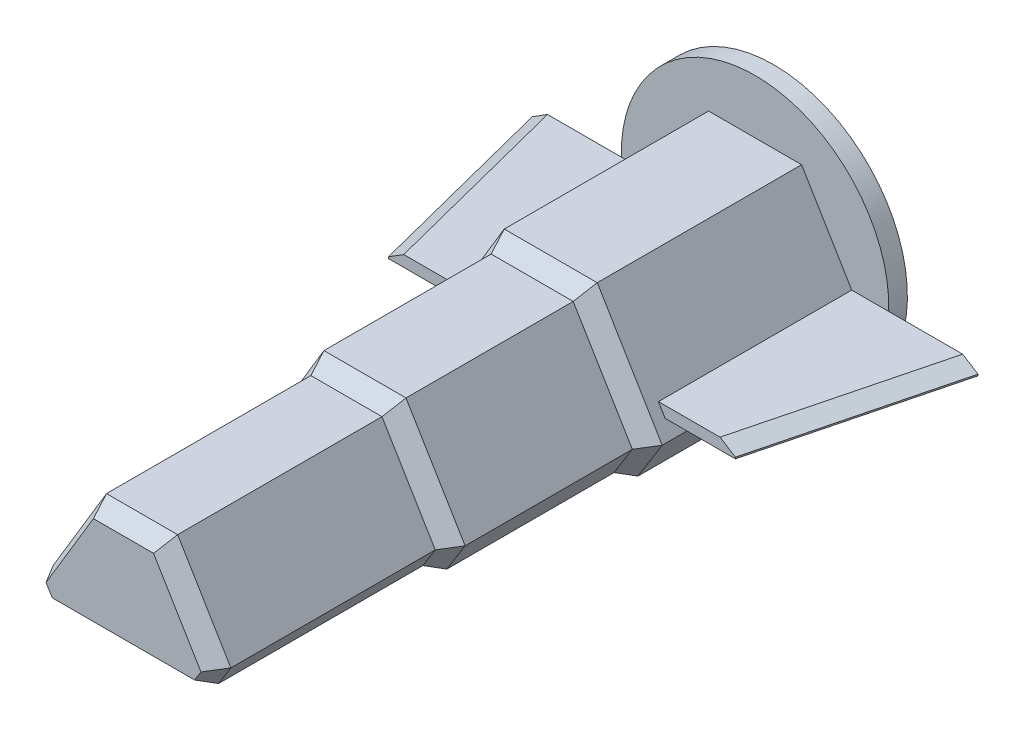
SolidWorks part; units mm, degrees
ref_plane "Front Plane" through (0, 0, 0) normal (0, 0, 1) x (1, 0, 0)
ref_plane "Top Plane" through (0, 0, 0) normal (0, 1, 0) x (1, 0, 0)
ref_plane "Right Plane" through (0, 0, 0) normal (1, 0, 0) x (0, 0, -1)
sketch "Sketch1" plane through (0, 0, 0) normal (0, 0, 1) x (1, 0, 0)
  line L0 (-26.9526, -9.3174) -> (-11.0422, 17.2)
  line L1 (23.4857, -19.8) -> (-23.4857, -19.8)
  line L2 (12.5143, 19.8) -> (-12.5143, 19.8)
  line L3 (12.5143, 19.8) -> (30, -9.3429)
  line L4 (23.4857, -19.8) -> (30, -9.3429)
  line L5 (11.0422, 17.2) -> (-11.0422, 17.2)
  line L6 (11.0422, 17.2) -> (26.9526, -9.3174)
  line L7 (-30, -9.3429) -> (-12.5143, 19.8)
  line L8 (-30, -9.3429) -> (-23.4857, -19.8)
  line L9 (22.0422, -17.2) -> (26.9526, -9.3174)
  line L10 (22.0422, -17.2) -> (-22.0422, -17.2)
  line L11 (-26.9526, -9.3174) -> (-22.0422, -17.2)
  point P0 (0, 0)
  point P4 (0, 19.8)
  point P13 (0, -19.8)
  dimension "D1" = 60
  dimension "D3" = 39.6
  dimension "D4" = 6.5143
  dimension "D5" = 10.4571
  dimension "D6" = 17.4857
  dimension "D2" = 2.6
extrude "Boss-Extrude1" add sketch "Sketch1" against normal blind 60
sketch "Sketch2" plane through (0, 0, 0) normal (0, 0, 1) x (1, 0, 0)
  line L6 (23.9053, -9.292) -> (9.5701, 14.6)
  line L7 (9.5701, 14.6) -> (-9.5701, 14.6)
  line L8 (-9.5701, 14.6) -> (-23.9053, -9.292)
  line L9 (-23.9053, -9.292) -> (-20.5986, -14.6)
  line L10 (-20.5986, -14.6) -> (20.5986, -14.6)
  line L11 (20.5986, -14.6) -> (23.9053, -9.292)
  line L12 (26.9526, -9.3174) -> (11.0422, 17.2)
  line L13 (11.0422, 17.2) -> (-11.0422, 17.2)
  line L14 (-11.0422, 17.2) -> (-26.9526, -9.3174)
  line L15 (-26.9526, -9.3174) -> (-22.0422, -17.2)
  line L16 (-22.0422, -17.2) -> (22.0422, -17.2)
  line L17 (22.0422, -17.2) -> (26.9526, -9.3174)
  line L18 (26.9526, -9.3174) -> (11.0422, 17.2)
  line L19 (11.0422, 17.2) -> (-11.0422, 17.2)
  line L20 (-11.0422, 17.2) -> (-26.9526, -9.3174)
  line L21 (-26.9526, -9.3174) -> (-22.0422, -17.2)
  line L22 (-22.0422, -17.2) -> (22.0422, -17.2)
  line L23 (22.0422, -17.2) -> (26.9526, -9.3174)
  dimension "D1" = 2.6
  dimension "D2" = 2.6
extrude "Boss-Extrude2" add sketch "Sketch2" along normal blind 50 and the other way blind 3 separate body
chamfer "Chamfer1" distance 5 distance2 2.6 6 edges at (0, -19.8, 0) (-26.7429, -14.5714, 0) (-21.2571, 5.2286, 0) (0, 19.8, 0) (26.7429, -14.5714, 0) (21.2571, 5.2286, 0) first distance on face at (0, -19.8, -30) first distance on face at (-26.7429, -14.5714, -30) first distance on face at (-21.2571, 5.2286, -30) first distance on face at (0, 19.8, -30) first distance on face at (26.7429, -14.5714, -30) first distance on face at (21.2571, 5.2286, -30)
sketch "Sketch8" plane through (0, 0, 50) normal (0, 0, 1) x (1, 0, 0)
  line L12 (19.1551, -12) -> (20.8579, -9.2665)
  line L13 (20.8579, -9.2665) -> (8.098, 12)
  line L14 (8.098, 12) -> (-8.098, 12)
  line L15 (-8.098, 12) -> (-20.8579, -9.2665)
  line L16 (-20.8579, -9.2665) -> (-19.1551, -12)
  line L17 (-19.1551, -12) -> (19.1551, -12)
  line L18 (19.1551, -12) -> (20.8579, -9.2665)
  line L19 (20.8579, -9.2665) -> (8.098, 12)
  line L20 (8.098, 12) -> (-8.098, 12)
  line L21 (-8.098, 12) -> (-20.8579, -9.2665)
  line L22 (-20.8579, -9.2665) -> (-19.1551, -12)
  line L23 (-19.1551, -12) -> (19.1551, -12)
  line L45 (23.9053, -9.292) -> (9.5701, 14.6)
  line L46 (20.5986, -14.6) -> (23.9053, -9.292)
  line L47 (-20.5986, -14.6) -> (20.5986, -14.6)
  line L48 (-23.9053, -9.292) -> (-20.5986, -14.6)
  line L49 (-9.5701, 14.6) -> (-23.9053, -9.292)
  line L50 (9.5701, 14.6) -> (-9.5701, 14.6)
  line L51 (23.9053, -9.292) -> (9.5701, 14.6)
  line L52 (20.5986, -14.6) -> (23.9053, -9.292)
  line L53 (-20.5986, -14.6) -> (20.5986, -14.6)
  line L54 (-23.9053, -9.292) -> (-20.5986, -14.6)
  line L55 (-9.5701, 14.6) -> (-23.9053, -9.292)
  line L56 (9.5701, 14.6) -> (-9.5701, 14.6)
  dimension "D1" = 5.2
  dimension "D2" = 2.6
extrude "Boss-Extrude3" add sketch "Sketch8" along normal blind 60 and the other way blind 8 separate body
chamfer "Chamfer2" distance 5 distance2 2.6 6 edges at (-18.9974, 3.9413, 50) (-24.4974, -13.2587, 50) (0, -17.2, 50) (24.4974, -13.2587, 50) (0, 17.2, 50) (18.9974, 3.9413, 50) first distance on face at (-18.9974, 3.9413, 23.5) first distance on face at (-24.4974, -13.2587, 23.5) first distance on face at (0, -17.2, 23.5) first distance on face at (24.4974, -13.2587, 23.5) first distance on face at (0, 17.2, 23.5) first distance on face at (18.9974, 3.9413, 23.5)
ref_plane "Plane2" through (60, 0, 0) normal (1, 0, 0) x (0, 0, -1)
sketch "Sketch9" plane through (60, 0, 0) normal (1, 0, 0) x (0, 0, -1)
  line L0 (60, -5.6775) -> (8, -5.6775)
  line L2 (60, -9.3429) -> (60, 19.8) construction
  line L3 (8, -5.6775) -> (8, -2.6775)
  line L4 (8, -2.6775) -> (60, -2.6775)
  line L5 (60, -2.6775) -> (60, -5.6775)
  dimension "D1" = 52
  dimension "D2" = 3
extrude "Boss-Extrude4" add sketch "Sketch9" against normal up to surface (33.9992 mm away) up to face at (21.2571, 5.2286, -32.5)
sketch "Sketch10" plane through (0, -2.6775, 0) normal (0, 1, 0) x (1, 0, 0)
  line L0 (60, 60) -> (60, 8)
  line L1 (60, 8) -> (46.7, 8)
  line L2 (26.0008, 8) -> (60, 8) construction
  line L3 (46.7, 8) -> (60, 60)
  spline S0 degree 1 poles (60, 60) (60, 8) knots 0 0 1 1
  line M3 (26.0008, 8) -> (60, 8)
  line M4 (60, 8) -> (60, 60)
  dimension "D1" = 13.3
extrude "Cut-Extrude1" cut sketch "Sketch10" against normal blind 28 contours L3 M3 M4 region at (55.5667, -2.6775, -25.3333)
chamfer "Chamfer3" distance 5 distance2 2.6 6 edges at (22.2519, -11.946, 110) (0, -14.6, 110) (-22.2519, -11.946, 110) (-16.7377, 2.654, 110) (0, 14.6, 110) (16.7377, 2.654, 110) first distance on face at (22.2519, -11.946, 76) first distance on face at (0, -14.6, 76) first distance on face at (-22.2519, -11.946, 76) first distance on face at (-16.7377, 2.654, 76) first distance on face at (0, 14.6, 76) first distance on face at (16.7377, 2.654, 76)
ref_plane "Plane4" through (0, 0, 110) normal (0, 0, 1) x (1, 0, 0)
sketch "Sketch12" plane through (0, 0, 110) normal (0, 0, 1) x (1, 0, 0)
  line L27 (-20.8579, -9.2665) -> (-19.1551, -12)
  line L28 (-8.098, 12) -> (-20.8579, -9.2665)
  line L29 (-19.1551, -12) -> (19.1551, -12)
  line L30 (19.1551, -12) -> (20.8579, -9.2665)
  line L31 (8.098, 12) -> (-8.098, 12)
  line L32 (20.8579, -9.2665) -> (8.098, 12)
  line L33 (-20.8579, -9.2665) -> (-19.1551, -12)
  line L34 (-8.098, 12) -> (-20.8579, -9.2665)
  line L35 (-19.1551, -12) -> (19.1551, -12)
  line L36 (19.1551, -12) -> (20.8579, -9.2665)
  line L37 (8.098, 12) -> (-8.098, 12)
  line L38 (20.8579, -9.2665) -> (8.098, 12)
  dimension "D1" = 0
extrude "Boss-Extrude5" add sketch "Sketch12" against normal blind 5
ref_plane "Plane5" through (-60, 0, 0) normal (1, 0, 0) x (0, 0, -1)
sketch "Sketch13" plane through (-60, 0, 0) normal (1, 0, 0) x (0, 0, -1)
  line L0 (60, -2.6775) -> (60, -5.6775)
  line L1 (60, -5.6775) -> (8, -5.6775)
  line L2 (8, -5.6775) -> (8, -2.6775)
  line L3 (8, -2.6775) -> (60, -2.6775)
  dimension "D1" = 52
extrude "Boss-Extrude6" add sketch "Sketch13" along normal up to surface (33.9992 mm away) up to face at (-21.2571, 5.2286, -32.5)
sketch "Sketch14" plane through (0, -2.6775, 0) normal (0, 1, 0) x (1, 0, 0)
  line L0 (-60, 60) -> (-60, 8)
  line L1 (-60, 8) -> (-46.7, 8)
  line L2 (-26.0008, 8) -> (-60, 8) construction
  line L3 (-46.7, 8) -> (-60, 60)
extrude "Cut-Extrude2" cut sketch "Sketch14" against normal blind 5
chamfer "Chamfer4" distance 4 distance2 2.6 1 edges at (-53.35, -2.6775, -34) first distance on face at (-39.6754, -2.6775, -34)
chamfer "Chamfer5" distance 2.6 distance2 4 1 edges at (53.35, -2.6775, -34) first distance on face at (53.35, -4.1775, -34)
sketch "Sketch16" plane through (0, 0, -60) normal (0, 0, -1) x (-1, 0, 0)
  circle A0 centre (0, -1.6292) radius 36
  dimension "D1" = 72
extrude "Boss-Extrude7" add sketch "Sketch16" along normal blind 5
